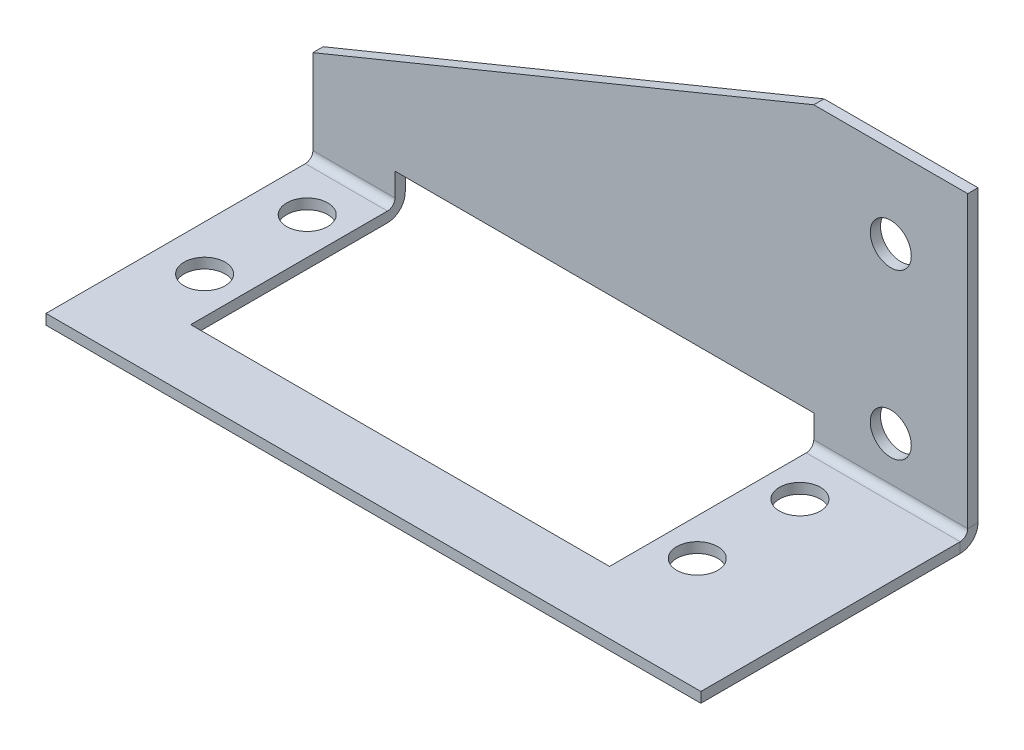
SolidWorks part; units mm, degrees
note: The reader was unsure of these and kept them because the rebuilt part matched: flange length of "Tôle pliée sur arête1".
material "Alliage 1060"
ref_plane "Plan de face" through (0, 0, 0) normal (0, 0, 1) x (1, 0, 0)
ref_plane "Plan de dessus" through (0, 0, 0) normal (0, 1, 0) x (1, 0, 0)
ref_plane "Plan de droite" through (0, 0, 0) normal (1, 0, 0) x (0, 0, -1)
sketch "Esquisse1" plane through (0, 0, 0) normal (0, 0, 1) x (1, 0, 0)
  line L0 (-48.8, 10) -> (0, 30)
  line L1 (15, 0) -> (-48.8, 0)
  line L2 (15, 0) -> (15, 30)
  line L3 (15, 30) -> (0, 30)
  line L4 (-48.8, 0) -> (-48.8, 10)
  line L5 (-40.8, 27.5513) -> (-40.8, 3.4) construction
  dimension "D1" = 30
  dimension "D2" = 15
  dimension "D3" = 8
  dimension "D4" = 10
sheet metal parameters "Tôlerie 1" thickness 1 parameters "D1"=0.7366
base flange "Tôle de base pliée1" sketch "Esquisse1" thickness 1 reverse thickness direction yes parameters "D1"=0.7366
edge flange "Tôle pliée sur arête1" sketch "Esquisse5" flange angle 90 flange length 26 flange position material inside bend radius 0.7366 thickness 1 relief rectangular parameters "D6"=10
sketch "Esquisse5" plane through (0, 0, 1) normal (0, -1, 0) x (1, 0, 0)
  line L0 (-48.8, 0) -> (15, 0) construction
  line L1 (-48.8, 0) -> (15, 0)
  line L2 (-48.8, 0) -> (-48.8, 26)
  line L3 (-48.8, 26) -> (15, 26)
  line L4 (15, 26) -> (15, 0)
bend "Pli d'arête1" bend radius 0.7366 bend angle 90 parameters "D5"=1
sketch "Esquisse6" plane through (0, 0, 0) normal (0, -1, 0) x (1, 0, 0)
  line L0 (-40.8, 3) -> (-40.8, 18.9) construction
  line L1 (-40.8, 20.9) -> (0, 20.9)
  line L2 (-40.8, 20.9) -> (-40.8, 0)
  line L3 (-40.8, 0) -> (0, 0)
  line L4 (0, 20.9) -> (0, 0)
  line L5 (-38.8, 20.9) -> (-2, 20.9) construction
  line L6 (15, 0) -> (-48.8, 0) construction
  line L7 (0, 18.9) -> (0, 3) construction
  circle A0 centre (3.6, 15.95) radius 2
  circle A1 centre (3.6, 5.95) radius 2
  circle A2 centre (-44.4, 15.95) radius 2
  circle A3 centre (-44.4, 5.95) radius 2
  arc A4 (-45.7151, 4.4432) -> (-45.7151, 7.4568) centre (-44.4, 5.95) ccw construction
  arc A5 (-45.7151, 14.4432) -> (-45.7151, 17.4568) centre (-44.4, 15.95) ccw construction
  arc A6 (5.1123, 7.6829) -> (5.1123, 4.2171) centre (3.6, 5.95) ccw construction
  arc A7 (5.1123, 17.6829) -> (5.1123, 14.2171) centre (3.6, 15.95) ccw construction
  dimension "D1" = 4
extrude "Enlèv. mat.-Extru.1" cut sketch "Esquisse6" against normal blind 4 normal cut yes
sketch "Esquisse7" plane through (0, 0, 1) normal (0, 0, 1) x (1, 0, 0)
  line L0 (7.5, 4.4934) -> (7.5, 29.2456) construction
  line L1 (0.5, 35.4) -> (0.5, -246.6) construction
  line L2 (14.5, 35.4) -> (14.5, 19.3843) construction
  line L3 (0, 1) -> (15, 1) construction
  line L4 (15, 30) -> (0, 30) construction
  circle A0 centre (7.5, 22) radius 2
  circle A1 centre (7.5, 6) radius 2
  dimension "D1" = 4
  dimension "D2" = 5
  dimension "D3" = 8
extrude "Enlèv. mat.-Extru.2" cut sketch "Esquisse7" against normal through all normal cut yes
flat pattern "Etat déplié1" [suppressed]
sketch "Lignes de pliage1" plane through (0, 0, 0) normal (0, 1, 0) x (-1, 0, 0)
bend of the flat pattern "Dépliage-<Pli d'arête1>1"
